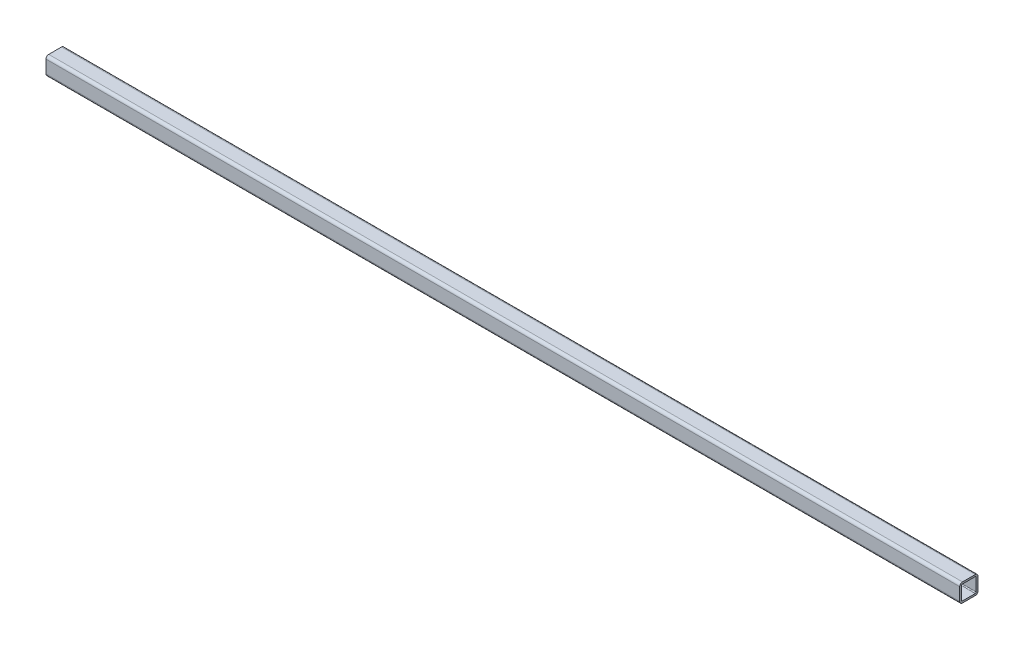
SolidWorks part; units mm, degrees
ref_plane "Спереди" through (0, 0, 0) normal (0, 0, 1) x (1, 0, 0)
ref_plane "Сверху" through (0, 0, 0) normal (0, 1, 0) x (1, 0, 0)
ref_plane "Справа" through (0, 0, 0) normal (1, 0, 0) x (0, 0, -1)
sketch "Эскиз1" plane through (0, 0, 0) normal (1, 0, 0) x (0, 0, -1)
  line L5 (1, 0) -> (15, 0)
  line L6 (0, 1) -> (0, 15)
  line L7 (1, 16) -> (15, 16)
  line L8 (16, 1) -> (16, 15)
  arc A4 (1, 0) -> (0, 1) centre (1, 1) cw
  arc A5 (15, 0) -> (16, 1) centre (15, 1) ccw
  arc A6 (15, 16) -> (16, 15) centre (15, 15) cw
  arc A7 (1, 16) -> (0, 15) centre (1, 15) ccw
  point P5 (0, 0)
  point P8 (0, 0)
  dimension "D1" = 1
extrude "Вытянуть-Тонкостенный1" add sketch "Эскиз1" along normal blind 1000 thin thin type one direction wall 2
